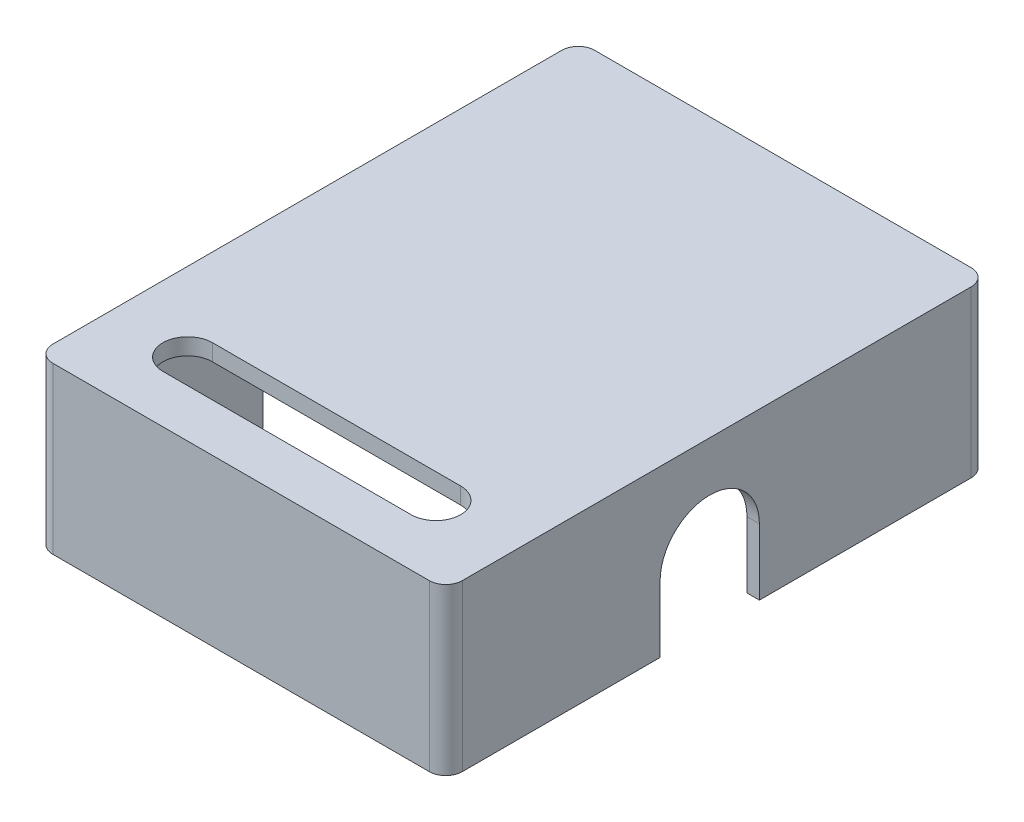
SolidWorks part; units mm, degrees
ref_plane "Front Plane" through (0, 0, 0) normal (0, 0, 1) x (1, 0, 0)
ref_plane "Top Plane" through (0, 0, 0) normal (0, 1, 0) x (1, 0, 0)
ref_plane "Right Plane" through (0, 0, 0) normal (1, 0, 0) x (0, 0, -1)
sketch "lid" plane through (0, 0, 0) normal (0, 1, 0) x (1, 0, 0)
  line L0 (-10.5, 22.6) -> (-10.5, -7.65)
  line L1 (12.75, -7.65) -> (12.75, 22.6)
  line L3 (-10, -8.15) -> (12.25, -8.15)
  line L5 (-10, 23.1) -> (12.25, 23.1)
  line L13 (-10.25, 23.85) -> (12.5, 23.85)
  line L14 (-11.25, 22.85) -> (-11.25, -7.9)
  line L15 (-10.25, -8.9) -> (12.5, -8.9)
  line L16 (13.5, 22.85) -> (13.5, -7.9)
  arc A0 (13.5, -7.9) -> (12.5, -8.9) centre (12.5, -7.9) cw
  arc A1 (-11.25, -7.9) -> (-10.25, -8.9) centre (-10.25, -7.9) ccw
  arc A2 (12.75, 22.6) -> (12.25, 23.1) centre (12.25, 22.6) ccw
  arc A3 (-10, 23.1) -> (-10.5, 22.6) centre (-10, 22.6) ccw
  arc A4 (-11.25, 22.85) -> (-10.25, 23.85) centre (-10.25, 22.85) cw
  arc A5 (12.5, 23.85) -> (13.5, 22.85) centre (12.5, 22.85) cw
  arc A6 (-10.5, -7.65) -> (-10, -8.15) centre (-10, -7.65) ccw
  arc A7 (12.25, -8.15) -> (12.75, -7.65) centre (12.25, -7.65) ccw
  point P0 (0, -8.9)
extrude "Boss-Extrude33" add sketch "lid" along normal blind 5 contours A0 A1 | A5 A3 L5 A2 region at (1.125, 0, -23.4395)
extrude "Boss-Extrude34" add sketch "lid<5>" along normal blind 1 from offset 5 contours A2 L5 A3 A0 | A0 A1 | A5 A3 L5 A2 region at (1.125, 0, -7.475) region at (1.125, 0, -23.4395)
sketch "lid<5>" plane through (0, 0, 0) normal (0, 1, 0) x (1, 0, 0) same geometry as "lid"
extrude "Boss-Extrude35" add sketch "lid<7>" against normal blind 4
sketch "lid<7>" plane through (0, 0, 0) normal (0, 1, 0) x (1, 0, 0) same geometry as "lid"
sketch "Sketch20" plane through (0, 6, 0) normal (0, 1, 0) x (1, 0, 0)
  line L0 (-6.5, -4.5) -> (8.5, -4.5) construction
  line L1 (-6.5, -3) -> (8.5, -3)
  line L2 (-6.5, -6) -> (8.5, -6)
  arc A0 (-6.5, -3) -> (-6.5, -6) centre (-6.5, -4.5) ccw
  arc A1 (8.5, -6) -> (8.5, -3) centre (8.5, -4.5) ccw
  point P2 (1, -4.5)
sketch "Sketch21" plane through (13.5, 0, 0) normal (1, 0, 0) x (0, 0, -1)
  line L0 (4.05, 0) -> (4.05, -4)
  line L2 (-7.9, -4) -> (22.85, -4) construction
  line L3 (4.05, -4) -> (10.05, -4)
  line L4 (10.05, -4) -> (10.05, 0)
  arc A0 (10.05, 0) -> (4.05, 0) centre (7.05, 0) ccw
extrude "Cut-Extrude2" cut sketch "Sketch21" against normal through all
extrude "Cut-Extrude3" cut sketch "Sketch20" against normal through all
sketch "Sketch22" plane through (0, 0, 8.15) normal (0, 0, -1) x (-1, 0, 0)
  line L0 (10, -4) -> (-12.25, -4) construction
  line L1 (-7.5, -4) -> (6, -4)
  line L2 (-7.5, -4) -> (-7.5, -2)
  line L3 (-7.5, -2) -> (6, -2)
  line L4 (6, -4) -> (6, -2)
extrude "Boss-Extrude37" add sketch "Sketch22" along normal blind 1.75
sketch "Sketch23" plane through (0, 0, -23.1) normal (0, 0, 1) x (1, 0, 0)
  line L0 (12.25, -4) -> (-10, -4) construction
  line L1 (-9, -1) -> (-6, -1)
  line L2 (-9, -1) -> (-9, -4)
  line L3 (-9, -4) -> (-6, -4)
  line L4 (-6, -1) -> (-6, -4)
  line L6 (8.25, -1) -> (11.25, -1)
  line L7 (8.25, -1) -> (8.25, -4)
  line L8 (8.25, -4) -> (11.25, -4)
  line L9 (11.25, -1) -> (11.25, -4)
extrude "Boss-Extrude38" add sketch "Sketch23" along normal blind 1.75
sketch "Sketch24" plane through (8.25, 0, 0) normal (-1, 0, 0) x (0, 0, 1)
  line L0 (-23.1, -4) -> (-21.35, -1)
  line L1 (-21.35, -1) -> (-21.35, -4)
  line L2 (-21.35, -4) -> (-23.1, -4)
extrude "Cut-Extrude4" cut sketch "Sketch24" against normal blind 3
extrude "Cut-Extrude5" cut sketch "Sketch24<2>" along normal blind 17.5
sketch "Sketch24<2>" plane through (8.25, 0, 0) normal (-1, 0, 0) x (0, 0, 1) same geometry as "Sketch24"
